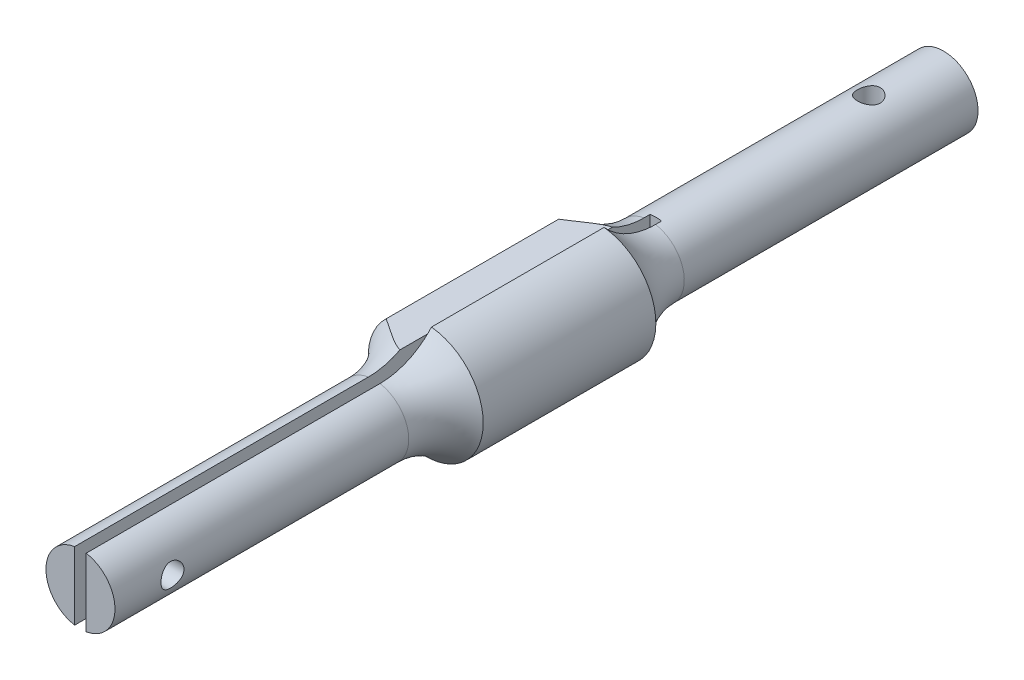
SolidWorks part; units mm, degrees
ref_plane "前视基准面" through (0, 0, 0) normal (0, 0, 1) x (1, 0, 0)
ref_plane "上视基准面" through (0, 0, 0) normal (0, 1, 0) x (1, 0, 0)
ref_plane "右视基准面" through (0, 0, 0) normal (1, 0, 0) x (0, 0, -1)
other "Configuration Table"
sketch "草图4" plane through (0, 0, 0) normal (0, 0, 1) x (1, 0, 0)
  circle A0 centre (0, 0) radius 5
  dimension "D1" = 10
extrude "凸台-拉伸2" add sketch "草图4" along normal blind 15
sketch "草图6" plane through (0, 0, 0) normal (0, 0, -1) x (-1, 0, 0)
  circle A0 centre (0, 0) radius 3
  dimension "D1" = 6
extrude "凸台-拉伸3" add sketch "草图6" along normal blind 30
sketch "草图7" plane through (0, 0, 15) normal (0, 0, 1) x (1, 0, 0)
  circle A0 centre (0, 0) radius 3
  dimension "D1" = 6
extrude "凸台-拉伸4" add sketch "草图7" along normal blind 30
sketch "草图5" plane through (0, 0, 0) normal (0, 0, -1) x (-1, 0, 0)
  line L0 (0, 0) -> (0, 5) construction
  line L1 (0.5, 3.628) -> (3.4405, 3.628)
  line L2 (-0.5, -2.9219) -> (0.5, -2.9219)
  line L3 (-0.5, -2.9219) -> (-0.5, 4.1248)
  line L5 (0.5, -2.9219) -> (0.5, 3.628)
  line L6 (-0.5, 4.1248) -> (-0.5, 4.9749)
  circle A0 centre (0, 0) radius 5 construction
  arc A1 (-0.5, 4.9749) -> (3.4405, 3.628) centre (0, 0) cw
  dimension "D1" = 1
  dimension "D2" = 0.5
extrude "切除-拉伸1" cut sketch "草图5" against normal blind 22 and the other way blind 5
fillet "圆角2" radius 6 1 edges at (0, -3, 0)
fillet "圆角3" radius 6 1 edges at (0, -3, 15)
sketch "草图8" plane through (0, 0, 0) normal (0, 1, 0) x (1, 0, 0)
  line L0 (3, 30) -> (-3, 30) construction
  circle A0 centre (0, 23.5) radius 1
  dimension "D1" = 2
  dimension "D2" = 6.5
extrude "切除-拉伸2" cut sketch "草图8" along normal blind 10 and the other way blind 10
sketch "草图9" plane through (0, 0, 0) normal (1, 0, 0) x (0, 0, -1)
  line L0 (-45, 3) -> (-45, -3) construction
  circle A0 centre (-40, 0) radius 1
  dimension "D2" = 2
  dimension "D1" = 5
extrude "切除-拉伸3" cut sketch "草图9" against normal mid plane 10
sketch "草图10" plane through (0, 0, 45) normal (0, 0, 1) x (1, 0, 0)
  line L0 (0.5, 4.9749) -> (0.5, 2.958) construction
  line L1 (-0.5, 3.628) -> (0.5, 3.628)
  line L2 (-0.5, 3.628) -> (-0.5, -3.1714)
  line L3 (-0.5, -3.1714) -> (0.5, -3.1714)
  line L4 (0.5, 3.628) -> (0.5, -3.1714)
extrude "切除-拉伸5" cut sketch "草图10" against normal blind 26
